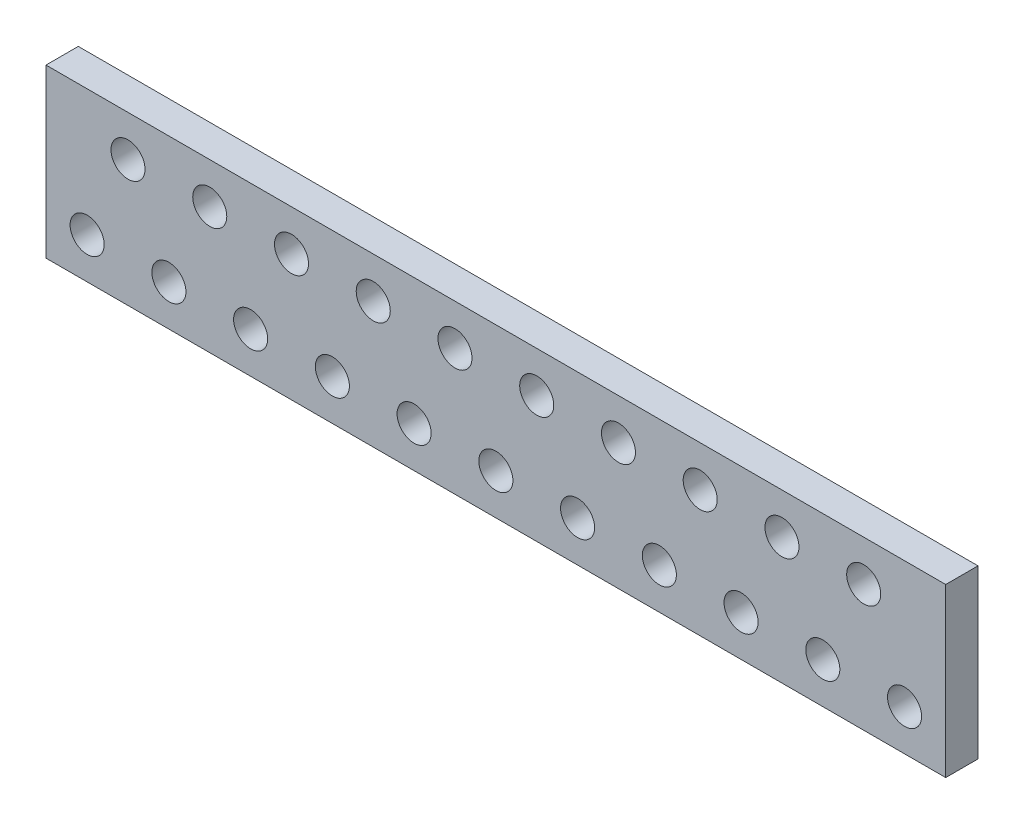
SolidWorks part; units mm, degrees
ref_plane "Front" through (0, 0, 0) normal (0, 0, 1) x (1, 0, 0)
ref_plane "Top" through (0, 0, 0) normal (0, 1, 0) x (1, 0, 0)
ref_plane "Right" through (0, 0, 0) normal (1, 0, 0) x (0, 0, -1)
sketch "Sketch1" plane through (0, 0, 0) normal (0, 0, 1) x (1, 0, 0)
  line L1 (-19.812, 3.683) -> (19.812, 3.683)
  line L2 (-19.812, 3.683) -> (-19.812, -3.683)
  line L3 (-19.812, -3.683) -> (19.812, -3.683)
  line L4 (19.812, 3.683) -> (19.812, -3.683)
extrude "PEEK" add sketch "Sketch1" along normal blind 1.4224 contours L1 L4 L3 L2
sketch "Sketch2" plane through (0, 0, 0) normal (0, 0, -1) x (-1, 0, 0)
  circle A0 centre (-18, -1.885) radius 0.75
  circle A1 centre (-14.4, -1.885) radius 0.75
  circle A2 centre (-10.8, -1.885) radius 0.75
  circle A3 centre (-7.2, -1.885) radius 0.75
  circle A4 centre (-3.6, -1.885) radius 0.75
  circle A5 centre (0, -1.885) radius 0.75
  circle A6 centre (3.6, -1.885) radius 0.75
  circle A7 centre (7.2, -1.885) radius 0.75
  circle A8 centre (10.8, -1.885) radius 0.75
  circle A9 centre (14.4, -1.885) radius 0.75
  circle A10 centre (18, -1.885) radius 0.75
  circle A11 centre (16.2, 1.885) radius 0.75
  circle A12 centre (12.6, 1.885) radius 0.75
  circle A13 centre (9, 1.885) radius 0.75
  circle A14 centre (5.4, 1.885) radius 0.75
  circle A15 centre (1.8, 1.885) radius 0.75
  circle A16 centre (-1.8, 1.885) radius 0.75
  circle A17 centre (-5.4, 1.885) radius 0.75
  circle A18 centre (-9, 1.885) radius 0.75
  circle A19 centre (-12.6, 1.885) radius 0.75
  circle A20 centre (-16.2, 1.885) radius 0.75
extrude "Cut-Extrude1" cut sketch "Sketch2" along direction (0, 0, -1) on the side against the normal up to surface (1.4224 mm away) up to face at (0, 0, 1.4224)
